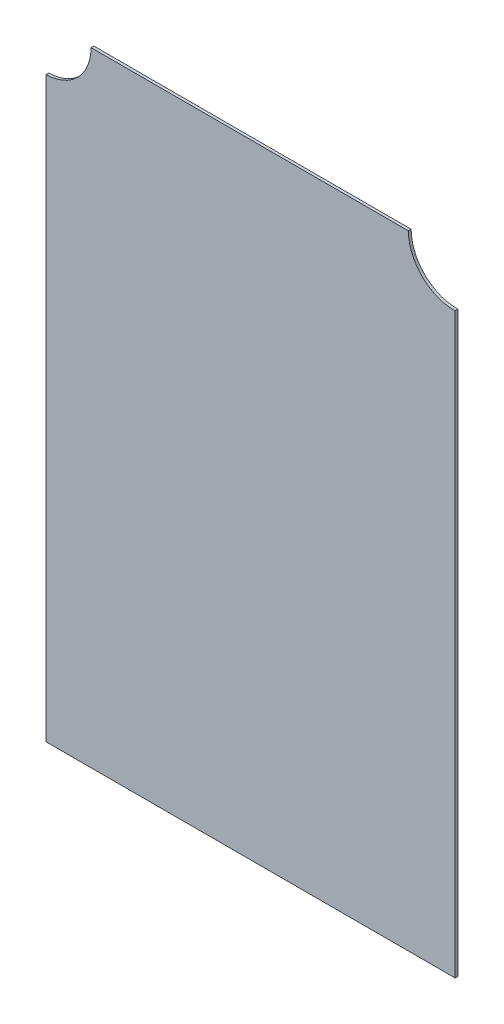
SolidWorks part; units mm, degrees
material "ДСП"
ref_plane "Спереди" through (0, 0, 0) normal (0, 0, 1) x (1, 0, 0)
ref_plane "Сверху" through (0, 0, 0) normal (0, 1, 0) x (1, 0, 0)
ref_plane "Справа" through (0, 0, 0) normal (1, 0, 0) x (0, 0, -1)
sketch "Эскиз1" plane through (0, 0, 0) normal (0, 0, 1) x (1, 0, 0)
  line L1 (0, 0) -> (446, 0)
  line L2 (0, 0) -> (0, 680)
  line L3 (0, 680) -> (446, 680)
  line L4 (446, 0) -> (446, 680)
  dimension "D1" = 680
  dimension "D2" = 446
extrude "Придание толщины" add sketch "Эскиз1" along normal blind 3
sketch "Эскиз3" plane through (0, 0, 3) normal (0, 0, 1) x (1, 0, 0)
  line L0 (0, 680) -> (0, 0) construction
  line L1 (0, 0) -> (446, 0) construction
  circle A0 centre (-1, 680) radius 50
  dimension "D1" = 100
  dimension "D2" = 1
  dimension "D3" = 680
extrude "Отверстие 1" cut sketch "Эскиз3" against normal blind 3
sketch "Эскиз4" plane through (0, 0, 3) normal (0, 0, 1) x (1, 0, 0)
  line L0 (0, 630.01) -> (0, 0) construction
  line L1 (0, 0) -> (446, 0) construction
  circle A0 centre (445, 680) radius 50
  dimension "D3" = 100
  dimension "D1" = 445
  dimension "D2" = 680
extrude "Отверстие 2" cut sketch "Эскиз4" against normal blind 3
sketch "Эскиз5" plane through (0, 0, 3) normal (0, 0, 1) x (1, 0, 0)
  line L0 (0, 630.01) -> (0, 0) construction
  line L1 (0, 0) -> (446, 0) construction
  circle A0 centre (0, 0) radius 4
  dimension "D1" = 8
extrude "Отверстие 3" [suppressed] cut sketch "Эскиз5" against normal blind 16
sketch "Эскиз6" plane through (0, 0, 3) normal (0, 0, 1) x (1, 0, 0)
  line L0 (0, 630.01) -> (0, 0) construction
  line L1 (0, 0) -> (446, 0) construction
  circle A0 centre (0, 0) radius 4
  dimension "D1" = 8
extrude "Отверстие 4" [suppressed] cut sketch "Эскиз6" against normal blind 16
sketch "Эскиз7" plane through (0, 0, 3) normal (0, 0, 1) x (1, 0, 0)
  line L0 (0, 630.01) -> (0, 0) construction
  line L1 (0, 0) -> (446, 0) construction
  circle A0 centre (0, 0) radius 4
  dimension "D1" = 8
extrude "Отверстие 5" [suppressed] cut sketch "Эскиз7" against normal blind 16
sketch "Эскиз8" plane through (0, 0, 3) normal (0, 0, 1) x (1, 0, 0)
  line L0 (0, 630.01) -> (0, 0) construction
  line L1 (0, 0) -> (446, 0) construction
  circle A0 centre (0, 0) radius 4
  dimension "D1" = 8
extrude "Отверстие 6" [suppressed] cut sketch "Эскиз8" against normal blind 16
sketch "Эскиз9" plane through (0, 0, 3) normal (0, 0, 1) x (1, 0, 0)
  line L0 (0, 630.01) -> (0, 0) construction
  line L1 (0, 0) -> (446, 0) construction
  circle A0 centre (0, 0) radius 4
  dimension "D1" = 8
extrude "Отверстие 7" [suppressed] cut sketch "Эскиз9" against normal blind 16
sketch "Эскиз10" plane through (0, 0, 3) normal (0, 0, 1) x (1, 0, 0)
  line L0 (0, 630.01) -> (0, 0) construction
  line L1 (0, 0) -> (446, 0) construction
  circle A0 centre (0, 0) radius 4
  dimension "D1" = 8
extrude "Отверстие 8" [suppressed] cut sketch "Эскиз10" against normal blind 16
sketch "Эскиз27" plane through (0, 0, 3) normal (0, 0, 1) x (1, 0, 0)
  line L2 (0, 630.01) -> (0, 0) construction
  line L3 (0, 0) -> (446, 0) construction
  circle A0 centre (0, 0) radius 4
  dimension "D1" = 8
  dimension "D3" = 0
extrude "Отверстие 9" [suppressed] cut sketch "Эскиз27" against normal blind 10
sketch "Эскиз29" plane through (0, 0, 3) normal (0, 0, 1) x (1, 0, 0)
  line L2 (0, 630.01) -> (0, 0) construction
  line L3 (0, 0) -> (446, 0) construction
  circle A0 centre (0, 0) radius 4
  dimension "D1" = 8
extrude "Отверстие 10" [suppressed] cut sketch "Эскиз29" against normal blind 10
sketch "Эскиз30" plane through (0, 0, 3) normal (0, 0, 1) x (1, 0, 0)
  line L1 (0, 0) -> (446, 0) construction
  line L3 (0, 630.01) -> (0, 0) construction
  circle A0 centre (0, 0) radius 4
  dimension "D1" = 8
extrude "Отверстие 11" [suppressed] cut sketch "Эскиз30" against normal blind 10
sketch "Эскиз31" plane through (0, 0, 3) normal (0, 0, 1) x (1, 0, 0)
  line L2 (0, 0) -> (446, 0) construction
  line L3 (0, 630.01) -> (0, 0) construction
  circle A0 centre (0, 0) radius 4
  dimension "D1" = 8
extrude "Отверстие 12" [suppressed] cut sketch "Эскиз31" against normal blind 10
sketch "Эскиз11" plane through (0, 680, 0) normal (0, 1, 0) x (1, 0, 0)
  line L0 (0, -3) -> (0, 0) construction
  line L1 (395, -3) -> (49, -3) construction
  circle A0 centre (0, -3) radius 2.5
  dimension "D3" = 0
  dimension "D1" = 5
extrude "Отверстие А1" [suppressed] cut sketch "Эскиз11" against normal blind 37
sketch "Эскиз12" plane through (0, 680, 0) normal (0, 1, 0) x (1, 0, 0)
  line L1 (0, -3) -> (0, 0) construction
  line L2 (395, -3) -> (49, -3) construction
  circle A0 centre (0, 5) radius 2.5
  dimension "D1" = 5
  dimension "D3" = 8
extrude "Отверстие А2" [suppressed] cut sketch "Эскиз12" against normal blind 37
sketch "Эскиз13" plane through (0, 680, 0) normal (0, 1, 0) x (1, 0, 0)
  line L1 (0, -3) -> (0, 0) construction
  line L2 (395, -3) -> (49, -3) construction
  circle A0 centre (0, -3) radius 4
  dimension "D1" = 8
  dimension "D3" = 0
extrude "Отверстие А3" [suppressed] cut sketch "Эскиз13" against normal blind 20
sketch "Эскиз14" plane through (0, 680, 0) normal (0, 1, 0) x (1, 0, 0)
  line L0 (0, -3) -> (0, 0) construction
  line L1 (395, -3) -> (49, -3) construction
  circle A0 centre (0, 5) radius 4
  dimension "D1" = 8
  dimension "D3" = 8
extrude "Отверстие А4" [suppressed] cut sketch "Эскиз14" against normal blind 20
sketch "Эскиз15" plane through (446, 0, 0) normal (1, 0, 0) x (0, 0, -1)
  line L0 (-3, 680) -> (0, 680) construction
  line L1 (-3, 0) -> (-3, 630.01) construction
  circle A0 centre (-3, 680) radius 2.5
  dimension "D2" = 0
  dimension "D3" = 0
  dimension "D1" = 5
extrude "Отверстие В1" [suppressed] cut sketch "Эскиз15" against normal blind 37
sketch "Эскиз16" plane through (446, 0, 0) normal (1, 0, 0) x (0, 0, -1)
  line L0 (-3, 680) -> (0, 680) construction
  line L1 (-3, 0) -> (-3, 630.01) construction
  circle A0 centre (-3, 680) radius 2.5
  dimension "D1" = 5
extrude "Отверстие В2" [suppressed] cut sketch "Эскиз16" against normal blind 37
sketch "Эскиз17" plane through (446, 0, 0) normal (1, 0, 0) x (0, 0, -1)
  line L1 (-3, 680) -> (0, 680) construction
  line L2 (-3, 0) -> (-3, 630.01) construction
  circle A0 centre (-3, 680) radius 4
  dimension "D1" = 8
  dimension "D2" = 0
  dimension "D3" = 0
extrude "Отверстие В3" [suppressed] cut sketch "Эскиз17" against normal blind 20
sketch "Эскиз18" plane through (446, 0, 0) normal (1, 0, 0) x (0, 0, -1)
  line L0 (-3, 680) -> (0, 680) construction
  line L1 (-3, 0) -> (-3, 630.01) construction
  circle A0 centre (-3, 680) radius 4
  dimension "D3" = 0
  dimension "D2" = 8
  dimension "D1" = 0
extrude "Отверстие В4" [suppressed] cut sketch "Эскиз18" against normal blind 20
sketch "Эскиз19" plane through (0, 0, 0) normal (0, -1, 0) x (1, 0, 0)
  line L0 (446, 3) -> (446, 0) construction
  line L1 (0, 3) -> (446, 3) construction
  circle A0 centre (446, 3) radius 2.5
  dimension "D2" = 0
  dimension "D3" = 0
  dimension "D1" = 5
extrude "Отверстие С1" [suppressed] cut sketch "Эскиз19" against normal blind 37
sketch "Эскиз20" plane through (0, 0, 0) normal (0, -1, 0) x (1, 0, 0)
  line L0 (446, 3) -> (446, 0) construction
  line L1 (0, 3) -> (446, 3) construction
  circle A0 centre (446, 3) radius 2.5
  dimension "D3" = 0
  dimension "D1" = 0
  dimension "D2" = 5
extrude "Отверстие С2" [suppressed] cut sketch "Эскиз20" against normal blind 37
sketch "Эскиз21" plane through (0, 0, 0) normal (0, -1, 0) x (1, 0, 0)
  line L0 (446, 3) -> (446, 0) construction
  line L1 (0, 3) -> (446, 3) construction
  circle A0 centre (446, 3) radius 4
  dimension "D1" = 8
  dimension "D2" = 0
  dimension "D3" = 0
extrude "Отверстие С3" [suppressed] cut sketch "Эскиз21" against normal blind 20
sketch "Эскиз22" plane through (0, 0, 0) normal (0, -1, 0) x (1, 0, 0)
  line L0 (446, 3) -> (446, 0) construction
  line L1 (0, 3) -> (446, 3) construction
  circle A0 centre (446, 3) radius 4
  dimension "D1" = 8
  dimension "D2" = 0
  dimension "D3" = 0
extrude "Отверстие С4" [suppressed] cut sketch "Эскиз22" against normal blind 20
sketch "Эскиз23" plane through (0, 0, 0) normal (-1, 0, 0) x (0, 0, 1)
  line L0 (3, 0) -> (0, 0) construction
  line L1 (3, 630.01) -> (3, 0) construction
  circle A0 centre (3, 0) radius 2.5
  dimension "D2" = 0
  dimension "D3" = 0
  dimension "D1" = 5
extrude "Отверстие Д1" [suppressed] cut sketch "Эскиз23" against normal blind 37
sketch "Эскиз24" plane through (0, 0, 0) normal (-1, 0, 0) x (0, 0, 1)
  line L0 (3, 0) -> (0, 0) construction
  line L1 (3, 630.01) -> (3, 0) construction
  circle A0 centre (3, 0) radius 2.5
  dimension "D2" = 0
  dimension "D3" = 0
  dimension "D1" = 5
extrude "Отверстие Д2" [suppressed] cut sketch "Эскиз24" against normal blind 37
sketch "Эскиз25" plane through (0, 0, 0) normal (-1, 0, 0) x (0, 0, 1)
  line L0 (3, 0) -> (0, 0) construction
  line L1 (3, 630.01) -> (3, 0) construction
  circle A0 centre (3, 0) radius 4
  dimension "D1" = 8
  dimension "D2" = 0
  dimension "D3" = 0
extrude "Отверстие Д3" [suppressed] cut sketch "Эскиз25" against normal blind 20
sketch "Эскиз26" plane through (0, 0, 0) normal (-1, 0, 0) x (0, 0, 1)
  line L0 (3, 0) -> (0, 0) construction
  line L1 (3, 630.01) -> (3, 0) construction
  circle A0 centre (3, 0) radius 4
  dimension "D1" = 8
  dimension "D2" = 0
  dimension "D3" = 0
extrude "Отверстие Д4" [suppressed] cut sketch "Эскиз26" against normal blind 20
equation "\"D1@Придание толщины\" = \"Thick\""
equation "\"D2@Эскиз1\"=\"Width\""
equation "\"D1@Эскиз1\"=\"Height\""
equation "\"D1\" = 100"
equation "\"X1\" = 1"
equation "\"Y1\" = 680"
equation "\"H1\" = 3"
equation "\"D1@Эскиз3\"=\"D1\""
equation "\"D2@Эскиз3\"=\"X1\""
equation "\"D3@Эскиз3\"=\"Y1\""
equation "\"D1@Отверстие 1\"=\"H1\""
equation "\"D2\" = 100"
equation "\"X2\" = 445"
equation "\"Y2\" = 680"
equation "\"H2\" = 3"
equation "\"D3\" = 0"
equation "\"X3\" = 0"
equation "\"Y3\" = 0"
equation "\"H3\" = 0"
equation "\"D4\" = 0"
equation "\"X4\" = 0"
equation "\"Y4\" = 0"
equation "\"H4\" = 0"
equation "\"D5\" = 0"
equation "\"X5\" = 0"
equation "\"Y5\" = 0"
equation "\"H5\" = 0"
equation "\"D6\" = 0"
equation "\"X6\" = 0"
equation "\"Y6\" = 0"
equation "\"H6\" = 0"
equation "\"D7\" = 0"
equation "\"X7\" = 0"
equation "\"Y7\" = 0"
equation "\"H7\" = 0"
equation "\"D8\" = 0"
equation "\"X8\" = 0"
equation "\"Y8\" = 0"
equation "\"H8\" = 0"
equation "\"D3@Эскиз4\"=\"D2\""
equation "\"D1@Эскиз4\"=\"X2\""
equation "\"D2@Эскиз4\"=\"Y2\""
equation "\"D1@Отверстие 2\"=\"H2\""
equation "\"D2@Эскиз5\"=\"X3\""
equation "\"D1@Эскиз5\"=\"D3\""
equation "\"D3@Эскиз5\"=\"Y3\""
equation "\"D1@Отверстие 3\" = \"H3\""
equation "\"D1@Эскиз6\"=\"D4\""
equation "\"D2@Эскиз6\"=\"X4\""
equation "\"D3@Эскиз6\"=\"Y4\""
equation "\"D1@Отверстие 4\" = \"H4\""
equation "\"D1@Эскиз7\"=\"D5\""
equation "\"D2@Эскиз7\"=\"X5\""
equation "\"D3@Эскиз7\"=\"Y5\""
equation "\"D1@Отверстие 5\" = \"H5\""
equation "\"D1@Эскиз8\"=\"D6\""
equation "\"D2@Эскиз8\"=\"X6\""
equation "\"D3@Эскиз8\"=\"Y6\""
equation "\"D1@Отверстие 6\" = \"H6\""
equation "\"D1@Эскиз9\"=\"D7\""
equation "\"D2@Эскиз9\"=\"X7\""
equation "\"D3@Эскиз9\"=\"Y7\""
equation "\"D1@Отверстие 7\" = \"H7\""
equation "\"D1@Эскиз10\"=\"D8\""
equation "\"D2@Эскиз10\"=\"X8\""
equation "\"D3@Эскиз10\"=\"Y8\""
equation "\"D1@Отверстие 8\" = \"H8\""
equation "\"Отверстие 1\"= IIF ( \"D1\" = 0 , \"suppressed\" , \"unsuppressed\" )"
equation "\"Отверстие 2\"= IIF ( \"D2\" = 0 , \"suppressed\" , \"unsuppressed\" )"
equation "\"Отверстие 3\"= IIF ( \"D3\" = 0 , \"suppressed\" , \"unsuppressed\" )"
equation "\"Отверстие 4\"= IIF ( \"D4\" = 0 , \"suppressed\" , \"unsuppressed\" )"
equation "\"Отверстие 5\"= IIF ( \"D5\" = 0 , \"suppressed\" , \"unsuppressed\" )"
equation "\"Отверстие 6\" = IIF ( \"D6\" = 0 , \"suppressed\" , \"unsuppressed\" )"
equation "\"Отверстие 7\"= IIF ( \"D7\" = 0 , \"suppressed\" , \"unsuppressed\" )"
equation "\"Отверстие 8\"= IIF ( \"D8\" = 0 , \"suppressed\" , \"unsuppressed\" )"
equation "\"DA1\"= 0"
equation "\"XA1\"= 0"
equation "\"YA1\"= 0"
equation "\"HA1\"= 0"
equation "\"DA2\"= 0"
equation "\"XA2\"= 0"
equation "\"YA2\"= 0"
equation "\"HA2\"= 0"
equation "\"DA3\"= 0"
equation "\"XA3\"= 0"
equation "\"YA3\"= 0"
equation "\"DA4\"= 0"
equation "\"XA4\"= 0"
equation "\"YA4\"= 0"
equation "\"HA4\"= 0"
equation "\"D1@Эскиз11\"=\"DA1\""
equation "\"D2@Эскиз11\"=\"XA1\""
equation "\"D3@Эскиз11\"=\"YA1\""
equation "\"D1@Отверстие А1\" = \"HA1\""
equation "\"D1@Эскиз12\"=\"DA2\""
equation "\"D2@Эскиз12\"=\"XA2\""
equation "\"HA3\"= 0"
equation "\"D1@Эскиз13\"=\"DA3\""
equation "\"D2@Эскиз13\"=\"XA3\""
equation "\"D3@Эскиз13\"=\"YA3\""
equation "\"D1@Отверстие А3\" = \"HA3\""
equation "\"D1@Отверстие А2\" = \"HA2\""
equation "\"D1@Эскиз14\"=\"DA4\""
equation "\"D2@Эскиз14\"=\"XA4\""
equation "\"Отверстие А1\"= IIF ( \"DA1\" = 0 , \"suppressed\" , \"unsuppressed\" )"
equation "\"Отверстие А2\"= IIF ( \"DA2\" = 0 , \"suppressed\" , \"unsuppressed\" )"
equation "\"Отверстие А3\"= IIF ( \"DA3\" = 0 , \"suppressed\" , \"unsuppressed\" )"
equation "\"Отверстие А4\"= IIF ( \"DA4\" = 0 , \"suppressed\" , \"unsuppressed\" )"
equation "\"DB1\"= 0"
equation "\"XB1\"= 0"
equation "\"YB1\"= 0"
equation "\"HB1\"= 0"
equation "\"DB2\"= 0"
equation "\"XB2\"= 0"
equation "\"YB2\"= 0"
equation "\"HB2\"= 0"
equation "\"DB3\"= 0"
equation "\"XB3\"= 0"
equation "\"YB3\"= 0"
equation "\"HB3\"= 0"
equation "\"DB4\"= 0"
equation "\"XB4\"= 0"
equation "\"YB4\"= 0"
equation "\"HB4\"= 0"
equation "\"DC1\"= 0"
equation "\"XC1\"= 0"
equation "\"YC1\"= 0"
equation "\"HC1\"= 0"
equation "\"DC2\"= 0"
equation "\"XC2\"= 0"
equation "\"YC2\"= 0"
equation "\"HC2\"= 0"
equation "\"DC3\"= 0"
equation "\"XC3\"= 0"
equation "\"YC3\"= 0"
equation "\"HC3\"= 0"
equation "\"DC4\"= 0"
equation "\"XC4\"= 0"
equation "\"YC4\"= 0"
equation "\"HC4\"= 0"
equation "\"DD1\"= 0"
equation "\"XD1\"= 0"
equation "\"YD1\"= 0"
equation "\"HD1\"= 0"
equation "\"DD2\"= 0"
equation "\"XD2\"= 0"
equation "\"YD2\"= 0"
equation "\"HD2\"= 0"
equation "\"DD3\"= 0"
equation "\"XD3\"= 0"
equation "\"YD3\"= 0"
equation "\"HD3\"= 0"
equation "\"DD4\"= 0"
equation "\"XD4\"= 0"
equation "\"YD4\"= 0"
equation "\"HD4\"= 0"
equation "\"D1@Эскиз15\"=\"DB1\""
equation "\"D2@Эскиз15\"=\"XB1\""
equation "\"D3@Эскиз15\"=\"YB1\""
equation "\"D1@Отверстие В1\" = \"HB1\""
equation "\"D1@Эскиз16\"=\"DB2\""
equation "\"D2@Эскиз16\"=\"XB2\""
equation "\"D3@Эскиз16\"=\"YB2\""
equation "\"D1@Отверстие В2\" = \"HB2\""
equation "\"D1@Эскиз17\"=\"DB3\""
equation "\"D2@Эскиз17\"=\"XB3\""
equation "\"D3@Эскиз17\"=\"YB3\""
equation "\"D1@Отверстие В3\" = \"HB3\""
equation "\"D1@Эскиз18\"=\"XB4\""
equation "\"D2@Эскиз18\"=\"DB4\""
equation "\"D3@Эскиз18\"=\"YB4\""
equation "\"D1@Отверстие В4\" = \"HB4\""
equation "\"D1@Эскиз19\"=\"DC1\""
equation "\"D2@Эскиз19\"=\"XC1\""
equation "\"D3@Эскиз19\"=\"YC1\""
equation "\"D1@Отверстие С1\" = \"HC1\""
equation "\"D1@Эскиз20\"=\"XC2\""
equation "\"D2@Эскиз20\"=\"DC2\""
equation "\"D3@Эскиз20\"=\"YC2\""
equation "\"D1@Отверстие С2\" = \"HC2\""
equation "\"D1@Эскиз21\"=\"DC3\""
equation "\"D2@Эскиз21\"=\"XC3\""
equation "\"D3@Эскиз21\"=\"YC3\""
equation "\"D1@Отверстие С3\" = \"HC3\""
equation "\"D1@Эскиз22\"=\"DC4\""
equation "\"D2@Эскиз22\"=\"XC4\""
equation "\"D3@Эскиз22\"=\"YC4\""
equation "\"D1@Отверстие С4\" = \"HC4\""
equation "\"D1@Эскиз23\"=\"DD1\""
equation "\"D2@Эскиз23\"=\"XD1\""
equation "\"D3@Эскиз23\"=\"YD1\""
equation "\"D1@Отверстие Д1\" = \"HD1\""
equation "\"D1@Эскиз24\"=\"DD2\""
equation "\"D2@Эскиз24\"=\"XD2\""
equation "\"D3@Эскиз24\"=\"YD2\""
equation "\"D1@Отверстие Д2\" = \"HD2\""
equation "\"D1@Эскиз25\"=\"DD3\""
equation "\"D2@Эскиз25\"=\"XD3\""
equation "\"D3@Эскиз25\"=\"YD3\""
equation "\"D1@Отверстие Д3\" = \"HD3\""
equation "\"D1@Эскиз26\"=\"DD4\""
equation "\"D2@Эскиз26\"=\"XD4\""
equation "\"D3@Эскиз26\"=\"YD4\""
equation "\"D1@Отверстие Д4\" = \"HD4\""
equation "\"Отверстие В1\"= IIF ( \"DB1\" = 0 , \"suppressed\" , \"unsuppressed\" )"
equation "\"Отверстие В2\"= IIF ( \"DB2\" = 0 , \"suppressed\" , \"unsuppressed\" )"
equation "\"Отверстие В3\"= IIF ( \"DB3\" = 0 , \"suppressed\" , \"unsuppressed\" )"
equation "\"Отверстие В4\"= IIF ( \"DB4\" = 0 , \"suppressed\" , \"unsuppressed\" )"
equation "\"Отверстие С1\"= IIF ( \"DC1\" = 0 , \"suppressed\" , \"unsuppressed\" )"
equation "\"Отверстие С2\"= IIF ( \"DC2\" = 0 , \"suppressed\" , \"unsuppressed\" )"
equation "\"Отверстие С3\"= IIF ( \"DC3\" = 0 , \"suppressed\" , \"unsuppressed\" )"
equation "\"Отверстие С4\"= IIF ( \"DC4\" = 0 , \"suppressed\" , \"unsuppressed\" )"
equation "\"Отверстие Д1\"= IIF ( \"DD1\" = 0 , \"suppressed\" , \"unsuppressed\" )"
equation "\"Отверстие Д2\"= IIF ( \"DD2\" = 0 , \"suppressed\" , \"unsuppressed\" )"
equation "\"Отверстие Д3\"= IIF ( \"DD3\" = 0 , \"suppressed\" , \"unsuppressed\" )"
equation "\"Отверстие Д4\"= IIF ( \"DD4\" = 0 , \"suppressed\" , \"unsuppressed\" )"
equation "\"D9\" = 0"
equation "\"X9\" = 0"
equation "\"Y9\" = 0"
equation "\"H9\" = 0"
equation "\"D10\" = 0"
equation "\"X10\" = 0"
equation "\"Y10\" = 0"
equation "\"H10\" = 0"
equation "\"D11\" = 0"
equation "\"X11\" = 0"
equation "\"Y11\" = 0"
equation "\"H11\" = 0"
equation "\"D12\" = 0"
equation "\"X12\" = 0"
equation "\"Y12\" = 0"
equation "\"H12\" = 0"
equation "\"D1@Эскиз27\"=\"D9\""
equation "\"D2@Эскиз27\"=\"X9\""
equation "\"D3@Эскиз27\"=\"Y9\""
equation "\"D1@Отверстие 9\" = \"H9\""
equation "\"D1@Эскиз29\"=\"D10\""
equation "\"D2@Эскиз29\"=\"X10\""
equation "\"D3@Эскиз29\"=\"Y10\""
equation "\"D1@Отверстие 10\" = \"H10\""
equation "\"D1@Эскиз30\"=\"D11\""
equation "\"D2@Эскиз30\"=\"X11\""
equation "\"D3@Эскиз30\"=\"Y11\""
equation "\"D1@Отверстие 11\" = \"H11\""
equation "\"D1@Эскиз31\"=\"D12\""
equation "\"D2@Эскиз31\"=\"X12\""
equation "\"D3@Эскиз31\"=\"Y12\""
equation "\"D1@Отверстие 12\" = \"H12\""
equation "\"Отверстие 9\"= IIF ( \"D9\" = 0 , \"suppressed\" , \"unsuppressed\" )"
equation "\"Отверстие 10\"= IIF ( \"D10\" = 0 , \"suppressed\" , \"unsuppressed\" )"
equation "\"Отверстие 11\"= IIF ( \"D11\" = 0 , \"suppressed\" , \"unsuppressed\" )"
equation "\"Отверстие 12\"= IIF ( \"D12\" = 0 , \"suppressed\" , \"unsuppressed\" )"
equation "\"Height\" = 680"
equation "\"Width\" = 446"
equation "\"Thick\" = 3"
